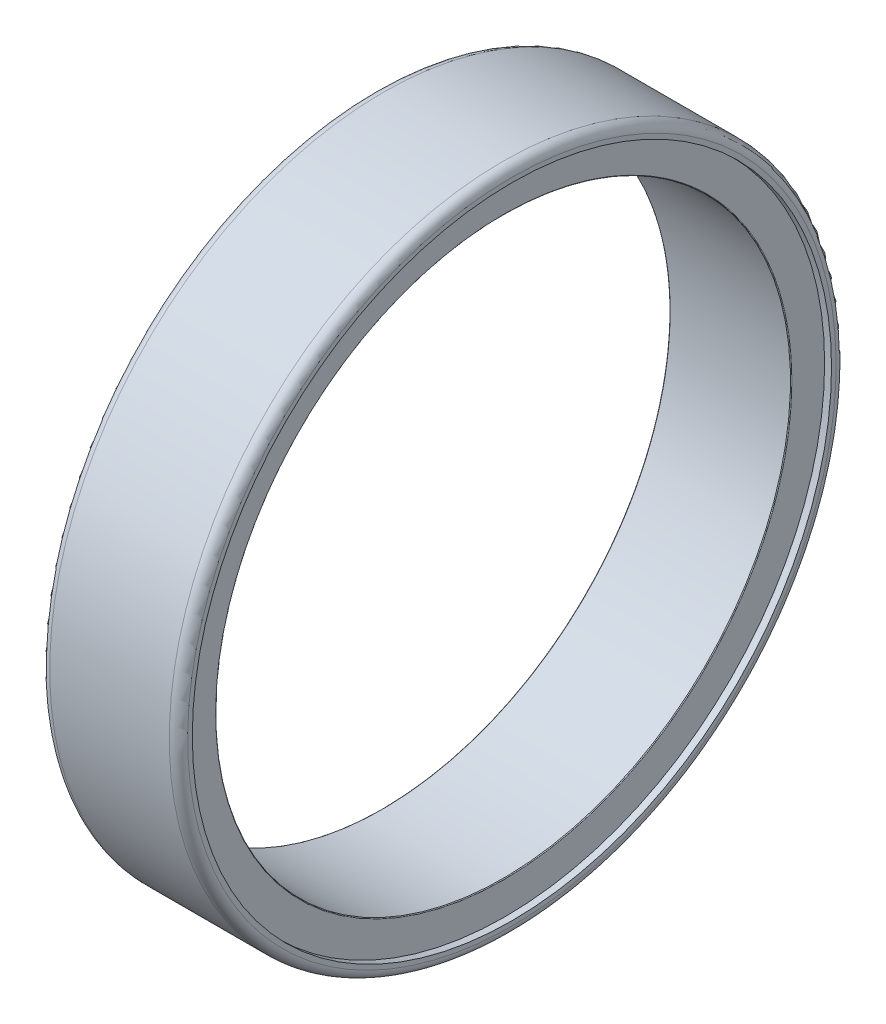
SolidWorks part; units mm, degrees
ref_plane "Plane1" through (0, 0, 0) normal (0, 0, 1) x (1, 0, 0)
ref_plane "Plane2" through (0, 0, 0) normal (0, 1, 0) x (1, 0, 0)
ref_plane "Plane3" through (0, 0, 0) normal (1, 0, 0) x (0, 0, -1)
sketch "Clipboard" plane through (0, 0, 0) normal (0, 0, 1) x (1, 0, 0)
  line L0 (-10, 0) -> (10, 0) construction
  line L1 (0, 0) -> (22.3471, -0.7804)
  line L2 (0, 0) -> (26.5838, 0.9283)
  line L3 (0, 0) -> (22.3471, -0.7804)
  line L4 (0, 0) -> (-50, -0.8728)
  dimension "BallCLRad" = 26.6
  dimension "Bore" = 50
sketch "InnRacSke" plane through (0, 0, 0) normal (0, 0, 1) x (1, 0, 0)
  line L0 (-5.4, 27.8) -> (-6, 27.8)
  line L1 (-6, 27.8) -> (-6, 28.2)
  line L2 (-5.2, 29) -> (5.2, 29)
  line L4 (6, 28.2) -> (6, 27.8)
  line L5 (6, 27.8) -> (5.4, 27.8)
  line L6 (5.4, 27.8) -> (5.4, 28.2)
  line L7 (5.4, 28.2) -> (-5.4, 28.2)
  line L8 (-5.4, 28.2) -> (-5.4, 27.8)
  line L9 (-31.75, 0) -> (31.75, 0) construction
  arc A0 (-6, 28.2) -> (-5.2, 29) centre (-5.2, 28.2) cw
  arc A2 (5.2, 29) -> (6, 28.2) centre (5.2, 28.2) cw
  dimension "D1" = 56.4
revolve "Race" add sketch "InnRacSke" angle 360 about L9 reverse direction yes
sketch "RolDetSke" plane through (0, 0, 0) normal (0, 0, 1) x (1, 0, 0)
  line L0 (-5.292, 28.1365) -> (-5.292, 26.6)
  line L1 (-5.292, 26.6) -> (5.292, 26.6)
  line L2 (5.292, 26.6) -> (5.292, 28.1365)
  line L3 (5.228, 28.2005) -> (-5.228, 28.2005)
  line L4 (-28.575, 26.6) -> (28.575, 26.6) construction
  arc A0 (5.292, 28.1365) -> (5.228, 28.2005) centre (5.228, 28.1365) ccw
  arc A1 (-5.228, 28.2005) -> (-5.292, 28.1365) centre (-5.228, 28.1365) ccw
  dimension "Roller_length" = 10.584
  dimension "Roller_diameter" = 3.201
revolve "RollerDetailed" [suppressed] add sketch "RolDetSke" angle 360 about L4 reverse direction yes
ref_axis "Axis1" through (-50, 0, 0) along (1, 0, 0)
sketch "CagSpiSke" plane through (0, 0, 0) normal (0, 0, 1) x (1, 0, 0)
  line L0 (5.7, 26.2799) -> (5.7, 26.9201)
  line L1 (5.7, 26.9201) -> (-5.7, 26.9201)
  line L2 (-5.7, 26.9201) -> (-5.7, 26.2799)
  line L3 (-5.7, 26.2799) -> (5.7, 26.2799)
  line L4 (-31.75, 0) -> (31.75, 0) construction
  dimension "D2" = 52.5598
  dimension "halfWidth" = 5.7
revolve "CageSpine" [suppressed] add sketch "CagSpiSke" angle 0.001 about L4
pattern_circular "RollersDetailed" [suppressed] count 2 every 180 about axis through (-50, 0, 0) along (1, 0, 0)
sketch "RolSimSke" plane through (0, 0, 0) normal (0, 0, 1) x (1, 0, 0)
  line L0 (-25.4, 0) -> (25.4, 0) construction
  line L2 (-5.228, 28.201) -> (5.228, 28.201)
  line L3 (-5.292, 28.137) -> (-5.292, 25.064)
  line L4 (-5.228, 25) -> (5.228, 25)
  line L5 (5.292, 28.137) -> (5.292, 25.064)
  arc A0 (-5.292, 25.064) -> (-5.228, 25) centre (-5.228, 25.064) ccw
  arc A1 (-5.228, 28.201) -> (-5.292, 28.137) centre (-5.228, 28.137) ccw
  arc A2 (5.292, 28.137) -> (5.228, 28.201) centre (5.228, 28.137) ccw
  arc A3 (5.228, 25) -> (5.292, 25.064) centre (5.228, 25.064) ccw
  point P10 (-5.292, 25)
  point P15 (5.292, 28.201)
  point P18 (5.292, 25)
  dimension "D1" = 0.064
  dimension "Bore" = 50
  dimension "Roller_length" = 10.584
  dimension "Roller_diameter" = 3.201
  dimension "halfWidth" = 5.292
revolve "RollersSimplified" add sketch "RolSimSke" angle 360 about L0
equation "\"BallCLRad@Clipboard\" =  ( \"D1@InnRacSke\" + \"Bore@Clipboard\" )  / 4"
equation "\"RollerCLRad@RolDetSke\" = \"BallCLRad@Clipboard\""
equation "\"halfCyl@InnRacSke\" = \"Cyl_Len@InnRacSke\" / 2"
equation "\"Roller_length@RolDetSke\" = \"Cyl_Len@InnRacSke\" * .98"
equation "\"halfLength@RolDetSke\" = \"Roller_length@RolDetSke\" / 2"
equation "\"Roller_diameter@RolDetSke\" =  ( \"D1@InnRacSke\" - \"Bore@Clipboard\" )  / 2 + .001"
equation "\"Roller_radius@RolDetSke\" = \"Roller_diameter@RolDetSke\" / 50"
equation "\"Cage_width@CagSpiSke\" =  ( \"Cyl_Len@InnRacSke\" + \"Width@InnRacSke\" )  / 2"
equation "\"halfWidth@CagSpiSke\" = \"Cage_width@CagSpiSke\" / 2"
equation "\"Cage_thickness@CagSpiSke\"  = \"Roller_diameter@RolDetSke\" / 5"
equation "\"D2@CagSpiSke\" =  \"RollerCLRad@RolDetSke\" * 2 - \"Cage_thickness@CagSpiSke\""
equation "\"Roller_length@RolSimSke\" = \"Cyl_Len@InnRacSke\" * .98"
equation "\"halfWidth@RolSimSke\" = \"Roller_length@RolSimSke\" / 2"
equation "\"D1@RolSimSke\" = \"Roller_radius@RolDetSke\""
equation "\"Roller_diameter@RolSimSke\" =  ( \"D1@InnRacSke\" - \"Bore@Clipboard\" )  / 2 + .001"
equation "\"Bore@RolSimSke\" = \"Bore@Clipboard\""
equation "\"Max_count@Clipboard\" = int( 3.14159265 / atn(( \"Roller_diameter@RolDetSke\" / 2) / sqr( \"RollerCLRad@RolDetSke\"  *  \"RollerCLRad@RolDetSke\" - ( \"Roller_diameter@RolDetSke\" / 2) *  ( \"Roller_diameter@RolDetSke\" / 2))))"
equation "\"Max_count@Clipboard\" = ((sgn( \"Max_count@Clipboard\" - \"Count@Clipboard\" )-1)*( \"Max_count@Clipboard\" - \"Count@Clipboard\" ))/-2+ \"Count@Clipboard\""
equation "\"Count@RollersDetailed\" = int( \"Show_count@Clipboard\" ) "
equation "\"Count@RollersDetailed\" = ((sgn( \"Count@RollersDetailed\" - \"Max_count@Clipboard\" )-1)*( \"Count@RollersDetailed\" - \"Max_count@Clipboard\" ))/-2+ \"Max_count@Clipboard\""
equation "\"Count@RollersDetailed\" = ((sgn( \"Count@RollersDetailed\" - \"Min_count@Clipboard\" )+1)*( \"Count@RollersDetailed\" - \"Min_count@Clipboard\"))/2 +\"Min_count@Clipboard\""
equation "\"Angle@RollersDetailed\" = 360.0 / \"Max_count@Clipboard\""
equation "\"Angle@CageSpine\" =  \"Angle@RollersDetailed\" * ( \"Count@RollersDetailed\" -1 + int( \"Count@RollersDetailed\" / \"Max_count@Clipboard\" ) )  + 0.001 -  int( \"Count@RollersDetailed\" / \"Max_count@Clipboard\" ) * 0.001"
equation "\"Angle@CageSpine\" =  \"Angle@CageSpine\" * int( \"Min_count@Clipboard\" / 2) + int(1 / \"Min_count@Clipboard\")  * 0.001"
